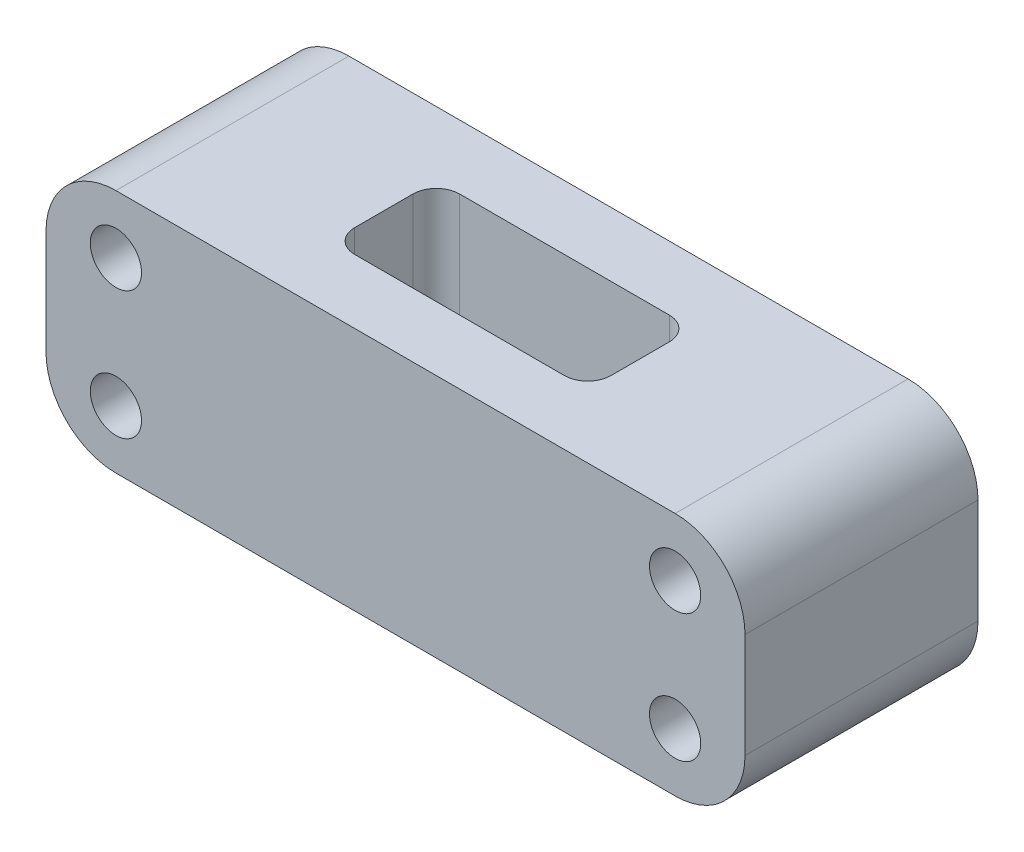
SolidWorks part; units mm, degrees
ref_plane "Front Plane" through (0, 0, 0) normal (0, 0, 1) x (1, 0, 0)
ref_plane "Top Plane" through (0, 0, 0) normal (0, 1, 0) x (1, 0, 0)
ref_plane "Right Plane" through (0, 0, 0) normal (1, 0, 0) x (0, 0, -1)
sketch "Sketch1" plane through (0, 0, 0) normal (0, 0, 1) x (1, 0, 0)
  line L1 (-30, 10.5) -> (30, 10.5)
  line L2 (-30, 10.5) -> (-30, -10.5)
  line L3 (-30, -10.5) -> (30, -10.5)
  line L4 (30, 10.5) -> (30, -10.5)
  line L5 (-30, 10.5) -> (30, -10.5) construction
  line L6 (-30, -10.5) -> (30, 10.5) construction
  point P0 (0, 0)
  dimension "D1" = 21
  dimension "D2" = 60
extrude "Boss-Extrude1" add sketch "Sketch1" along normal blind 10 and the other way blind 10
fillet "Fillet1" radius 6 4 edges at (30, -10.5, 0) (30, 10.5, 0) (-30, -10.5, 0) (-30, 10.5, 0)
sketch "Sketch2" plane through (0, 0, 10) normal (0, 0, 1) x (1, 0, 0)
  line L0 (-26.5638, 0) -> (32.3709, 0) construction
  line L1 (-24, 5.5) -> (24, 5.5) construction
  line L2 (0, 0) -> (0, 18.154) construction
  line L3 (24, 10.5) -> (-24, 10.5) construction
  line L4 (-9.9403, 10.5) -> (-44.1311, 10.5) construction
  line L5 (-24, -5.5) -> (24, -5.5) construction
  circle A0 centre (-24, 5.5) radius 2.2
  circle A1 centre (24, 5.5) radius 2.2
  circle A2 centre (24, -5.5) radius 2.2
  circle A3 centre (-24, -5.5) radius 2.2
  dimension "D1" = 4.4
  dimension "D2" = 48
  dimension "D3" = 11
extrude "Cut-Extrude1" cut sketch "Sketch2" against normal through all
sketch "Sketch3" plane through (0, 10.5, 0) normal (0, 1, 0) x (1, 0, 0)
  line L1 (9, -4.5) -> (-9, -4.5)
  line L2 (11, -2.5) -> (11, 2.5)
  line L3 (9, 4.5) -> (-9, 4.5)
  line L4 (-11, -2.5) -> (-11, 2.5)
  line L5 (11, -4.5) -> (-11, 4.5) construction
  line L6 (11, 4.5) -> (-11, -4.5) construction
  arc A0 (11, 2.5) -> (9, 4.5) centre (9, 2.5) ccw
  arc A1 (9, -4.5) -> (11, -2.5) centre (9, -2.5) ccw
  arc A2 (-9, -4.5) -> (-11, -2.5) centre (-9, -2.5) cw
  arc A3 (-9, 4.5) -> (-11, 2.5) centre (-9, 2.5) ccw
  point P0 (0, 0)
  dimension "D1" = 2
  dimension "D2" = 22
  dimension "D3" = 9
extrude "Cut-Extrude2" cut sketch "Sketch3" against normal through all
